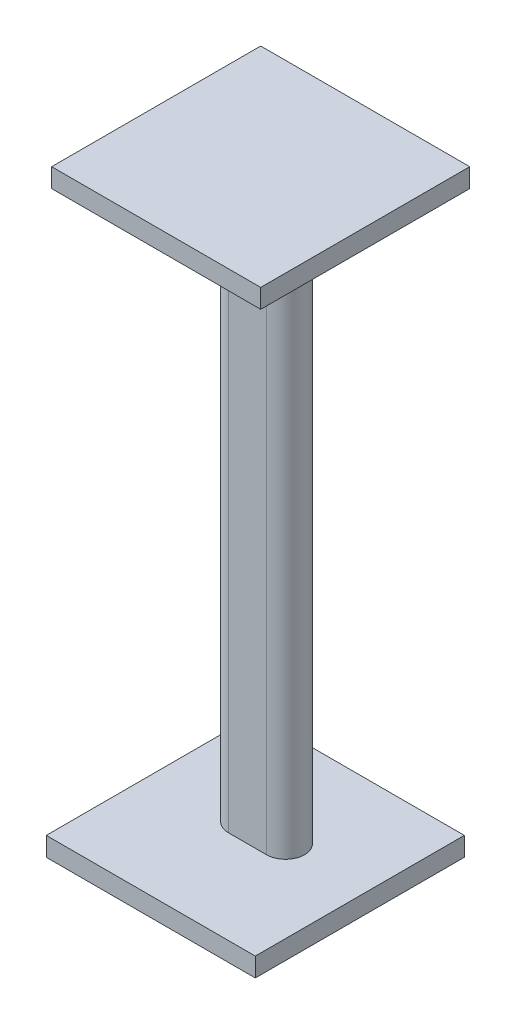
SolidWorks part; units mm, degrees
ref_plane "Front" through (0, 0, 0) normal (0, 0, 1) x (1, 0, 0)
ref_plane "Top" through (0, 0, 0) normal (0, 1, 0) x (1, 0, 0)
ref_plane "Right" through (0, 0, 0) normal (1, 0, 0) x (0, 0, -1)
ref_axis "X" through (-88.99, 0, 0) along (1, 0, 0)
ref_axis "Y" through (0, 55, 0) along (0, -1, 0)
ref_axis "Z" through (0, 0, -88.99) along (0, 0, 1)
sketch "Sketch1" plane through (0, 0, 0) normal (0, 1, 0) x (1, 0, 0)
  line L1 (-391.7729, 296.4549) -> (27.3271, 296.4549)
  line L2 (-391.7729, 296.4549) -> (-391.7729, -122.6451)
  line L3 (-391.7729, -122.6451) -> (27.3271, -122.6451)
  line L4 (27.3271, 296.4549) -> (27.3271, -122.6451)
  dimension "D1" = 419.1
  dimension "D2" = 419.1
extrude "Boss-Extrude1" add sketch "Sketch1" along normal blind 38.1
sketch "Sketch4" plane through (0, 38.1, 0) normal (0, 1, 0) x (1, 0, 0)
  line L1 (-213.4321, 140.7133) -> (-137.2321, 140.7133)
  line L3 (-213.4321, 64.5133) -> (-137.2321, 64.5133)
  arc A0 (-213.4321, 140.7133) -> (-213.4321, 64.5133) centre (-213.4321, 102.6133) ccw
  arc A1 (-137.2321, 64.5133) -> (-137.2321, 140.7133) centre (-137.2321, 102.6133) ccw
extrude "Boss-Extrude2" add sketch "Sketch4" along normal blind 1117.6
sketch "Sketch6" plane through (0, 1155.7, 0) normal (0, 1, 0) x (1, 0, 0)
  line L1 (27.3817, 307.2516) -> (-391.7183, 307.2516)
  line L2 (27.3817, 307.2516) -> (27.3817, -111.8484)
  line L3 (27.3817, -111.8484) -> (-391.7183, -111.8484)
  line L4 (-391.7183, 307.2516) -> (-391.7183, -111.8484)
  dimension "D1" = 419.1
  dimension "D2" = 419.1
extrude "Boss-Extrude4" add sketch "Sketch6" along normal blind 38.1
